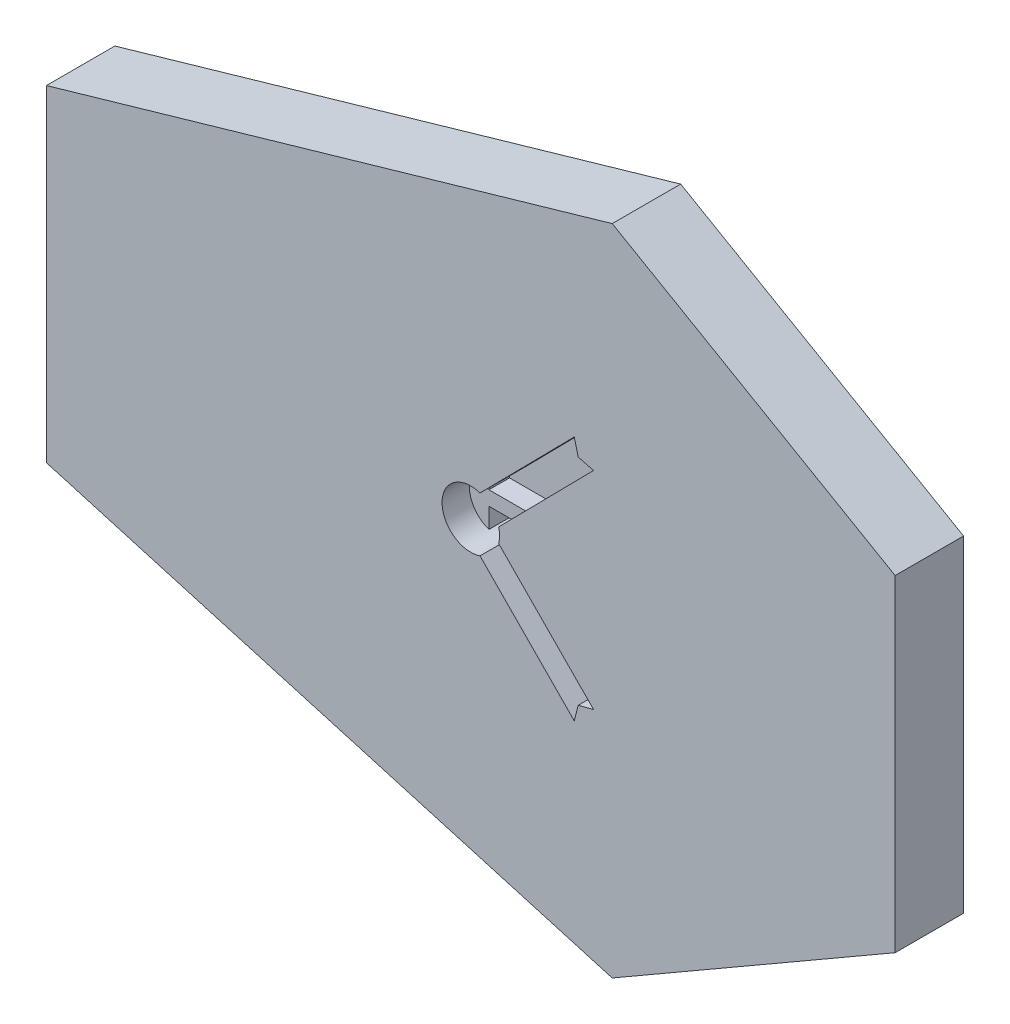
SolidWorks part; units mm, degrees
ref_plane "Front Plane" through (0, 0, 0) normal (0, 0, 1) x (1, 0, 0)
ref_plane "Top Plane" through (0, 0, 0) normal (0, 1, 0) x (1, 0, 0)
ref_plane "Right Plane" through (0, 0, 0) normal (1, 0, 0) x (0, 0, -1)
sketch "Sketch2" plane through (0, 0, 0) normal (0, 0, 1) x (1, 0, 0)
  line L0 (-36.15, 11.9319) -> (-36.15, -11.9319) construction
  line L1 (5.1833, -23.8638) -> (-36.15, -11.9319) construction
  line L2 (5.1833, -23.8638) -> (25.85, -11.9319) construction
  line L3 (25.85, -11.9319) -> (25.85, 11.9319) construction
  line L4 (25.85, 11.9319) -> (5.1833, 23.8638) construction
  line L5 (-36.15, 11.9319) -> (5.1833, 23.8638) construction
  line L6 (-36.15, 11.9319) -> (-36.15, -11.9319)
  line L7 (5.1833, -23.8638) -> (-36.15, -11.9319)
  line L8 (5.1833, -23.8638) -> (25.85, -11.9319)
  line L9 (25.85, -11.9319) -> (25.85, 11.9319)
  line L10 (25.85, 11.9319) -> (5.1833, 23.8638)
  line L11 (-36.15, 11.9319) -> (5.1833, 23.8638)
extrude "Boss-Extrude1" add sketch "Sketch2" along normal blind 1.5
sketch "Sketch4" plane through (0, 0, 1.5) normal (0, 0, 1) x (1, 0, 0)
  line L6 (5.1833, 23.8638) -> (-36.15, 11.9319)
  line L7 (-36.15, 11.9319) -> (-36.15, -11.9319)
  line L8 (-36.15, -11.9319) -> (5.1833, -23.8638)
  line L9 (5.1833, -23.8638) -> (25.85, -11.9319)
  line L10 (25.85, -11.9319) -> (25.85, 11.9319)
  line L11 (25.85, 11.9319) -> (5.1833, 23.8638)
  line L12 (5.1833, 23.8638) -> (-36.15, 11.9319)
  line L13 (-36.15, 11.9319) -> (-36.15, -11.9319)
  line L14 (-36.15, -11.9319) -> (5.1833, -23.8638)
  line L15 (5.1833, -23.8638) -> (25.85, -11.9319)
  line L16 (25.85, -11.9319) -> (25.85, 11.9319)
  line L17 (25.85, 11.9319) -> (5.1833, 23.8638)
  circle A0 centre (-5.15, 0) radius 2.1
  point P9 (-5.15, 0)
  dimension "D2" = 4.2
  dimension "D1" = 0
extrude "Boss-Extrude2" add sketch "Sketch4" along normal blind 3.5
sketch "Sketch5" plane through (0, 0, 5) normal (0, 0, 1) x (1, 0, 0)
  line L0 (-13.0004, 7.8504) -> (-16.8732, 6.8495) construction
  line L1 (-16.8732, 6.8495) -> (-16.1225, 3.9449) construction
  line L2 (-10.5382, 5.3882) -> (-16.1225, 3.9449) construction
  line L3 (-9.0949, 10.9725) -> (-10.5382, 5.3882) construction
  line L4 (-11.9995, 11.7232) -> (-9.0949, 10.9725) construction
  line L5 (-11.9995, 11.7232) -> (-13.0004, 7.8504) construction
  line L6 (-13.0004, 7.8504) -> (-16.8732, 6.8495) construction
  line L7 (-16.8732, 6.8495) -> (-16.1225, 3.9449) construction
  line L8 (-10.5382, 5.3882) -> (-16.1225, 3.9449) construction
  line L9 (-9.0949, 10.9725) -> (-10.5382, 5.3882) construction
  line L10 (-11.9995, 11.7232) -> (-9.0949, 10.9725) construction
  line L11 (-11.9995, 11.7232) -> (-13.0004, 7.8504) construction
  line L12 (-7.184, 0.5223) -> (-14.1193, 7.5613) construction
  line L13 (-14.1193, 7.5613) -> (-13.0004, 7.8504) construction
  line L14 (-12.7087, 8.9791) -> (-5.8221, 1.9895) construction
  line L15 (-13.0004, 7.8504) -> (-12.7087, 8.9791) construction
  line L16 (-6.4, 3.7) -> (-3.9, -3.7) construction
  line L17 (-5.15, 0) -> (-5.15, 20.8808) construction
  line L18 (-12.7087, 8.9791) -> (-14.1193, 7.5613) construction
  line L19 (-13.414, 8.2702) -> (-13.0004, 7.8504) construction
  line L20 (-7.184, 0.5223) -> (-4.4779, 0.5223) construction
  line L21 (-4.4779, 0.5223) -> (-4.4779, 1.9895) construction
  line L22 (-4.4779, 1.9895) -> (-5.8221, 1.9895)
  line L23 (5.1833, 23.8638) -> (-36.15, 11.9319) construction
  line L24 (3.114, 8.2702) -> (2.7004, 7.8504) construction
  line L25 (2.4087, 8.9791) -> (3.8193, 7.5613) construction
  line L26 (1.6995, 11.7232) -> (2.7004, 7.8504) construction
  line L27 (1.6995, 11.7232) -> (-1.2051, 10.9725) construction
  line L28 (-1.2051, 10.9725) -> (0.2382, 5.3882) construction
  line L29 (0.2382, 5.3882) -> (5.8225, 3.9449) construction
  line L30 (6.5732, 6.8495) -> (5.8225, 3.9449) construction
  line L31 (2.7004, 7.8504) -> (6.5732, 6.8495) construction
  line L32 (-5.8221, 0.5223) -> (-5.8221, 1.9895)
  line L33 (-3.116, 0.5223) -> (-5.8221, 0.5223)
  line L34 (2.7004, 7.8504) -> (2.4087, 8.9791)
  line L35 (2.4087, 8.9791) -> (-4.4779, 1.9895)
  line L36 (3.8193, 7.5613) -> (2.7004, 7.8504)
  line L37 (-3.116, 0.5223) -> (3.8193, 7.5613)
  circle A0 centre (-5.15, 0) radius 2.1 construction
  dimension "D1" = 2
extrude "Cut-Extrude1" cut sketch "Sketch5" against normal up to surface (3.5 mm away) up to face at (-3.05, 0, 1.5)
sketch "Sketch9" plane through (0, 0, 1.5) normal (0, 0, 1) x (1, 0, 0)
  line L8 (2.4087, 8.9791) -> (2.7004, 7.8504)
  line L9 (2.7004, 7.8504) -> (3.8193, 7.5613)
  line L10 (3.8193, 7.5613) -> (2.009, 5.7239)
  line L11 (-3.116, 0.5223) -> (3.8193, 7.5613) construction
  line L12 (2.009, 5.7239) -> (0.5844, 7.1276)
  line L13 (2.4087, 8.9791) -> (-4.4779, 1.9895) construction
  line L14 (0.5844, 7.1276) -> (2.4087, 8.9791)
  dimension "D1" = 2
extrude "Cut-Extrude2" cut sketch "Sketch9" against normal through all
sketch "Sketch7" plane through (0, 0, 5) normal (0, 0, 1) x (1, 0, 0)
  line L0 (-7.25, 0) -> (-3.05, 0) construction
  line L1 (-5.15, 2.1) -> (-5.15, -2.1) construction
  arc A0 (-4.4779, 1.9895) -> (-3.116, 0.5223) centre (-5.15, 0) ccw construction
ref_plane "Plane1" through (0, 0, 0) normal (0, -1, 0) x (1, 0, 0)
mirror "Mirror1" about plane through (0, 0, 0) normal (0, -1, 0) of "Cut-Extrude2", "Cut-Extrude1"
sketch "Sketch8" plane through (0, 0, 1.5) normal (0, 0, 1) x (1, 0, 0)
  line L2 (-5.8221, 0.5223) -> (-5.8221, 1.9895) construction
  line L3 (-3.116, 0.5223) -> (-5.8221, 0.5223) construction
  line L4 (-5.8221, 0.5223) -> (-5.8221, 1.9895)
  line L5 (-3.116, 0.5223) -> (-5.8221, 0.5223)
  line L6 (-7.25, 0) -> (-3.05, 0) construction
  line L7 (-3.116, -0.5223) -> (-5.8221, -0.5223)
  line L8 (-5.8221, -0.5223) -> (-5.8221, -1.9895)
  arc A0 (-3.116, -0.5223) -> (-3.116, 0.5223) centre (-5.15, 0) ccw construction
  arc A1 (-3.116, -0.5223) -> (-3.116, 0.5223) centre (-5.15, 0) ccw
  arc A2 (-4.4779, 1.9895) -> (-4.4779, -1.9895) centre (-5.15, 0) ccw construction
  arc A3 (-5.8221, 1.9895) -> (-5.8221, -1.9895) centre (-5.15, 0) ccw
extrude "Boss-Extrude3" add sketch "Sketch8" along normal blind 1.5
